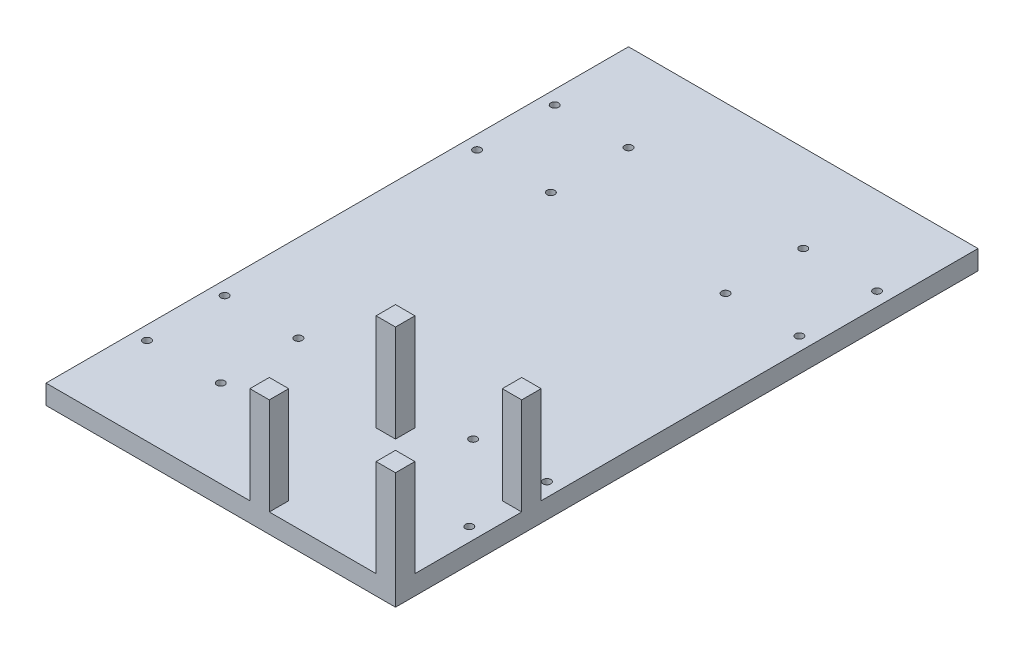
SolidWorks part; units mm, degrees
material "Pine"
ref_plane "Front Plane" through (0, 0, 0) normal (0, 0, 1) x (1, 0, 0)
ref_plane "Top Plane" through (0, 0, 0) normal (0, 1, 0) x (1, 0, 0)
ref_plane "Right Plane" through (0, 0, 0) normal (1, 0, 0) x (0, 0, -1)
sketch "Sketch3" plane through (0, 0, 0) normal (0, 1, 0) x (1, 0, 0)
  line L1 (-90, -150) -> (90, -150)
  line L2 (-90, -150) -> (-90, 150)
  line L3 (-90, 150) -> (90, 150)
  line L4 (90, -150) -> (90, 150)
  line L5 (-90, -150) -> (90, 150) construction
  line L6 (-90, 150) -> (90, -150) construction
  point P0 (0, 0)
  dimension "D1" = 180
  dimension "D2" = 300
extrude "Boss-Extrude1" add sketch "Sketch3" along normal blind 10
sketch "Sketch4" plane through (0, 10, 0) normal (0, 1, 0) x (1, 0, 0)
  line L0 (90, -150) -> (90, 150) construction
  line L1 (90, -150) -> (80, -150)
  line L2 (90, -150) -> (90, -140)
  line L3 (90, -75) -> (80, -75)
  line L4 (15, -150) -> (15, -140)
  line L5 (-90, -150) -> (90, -150) construction
  line L6 (25, -150) -> (25, -140)
  line L7 (80, -75) -> (80, -85)
  line L8 (25, -75) -> (15, -75)
  line L9 (25, -150) -> (15, -150)
  line L10 (15, -140) -> (25, -140)
  line L11 (15, -85) -> (25, -85)
  line L12 (80, -85) -> (90, -85)
  line L13 (80, -140) -> (90, -140)
  line L14 (15, -85) -> (15, -75)
  line L15 (25, -85) -> (25, -75)
  line L16 (80, -140) -> (80, -150)
  line L17 (90, -85) -> (90, -75)
  point P20 (85, -140)
  dimension "D1" = 0
  dimension "D2" = 0
  dimension "D3" = 75
  dimension "D4" = 75
  dimension "D5" = 10
  dimension "D6" = 10
  dimension "D7" = 10
  dimension "D8" = 10
  dimension "D9" = 10
extrude "Boss-Extrude2" add sketch "Sketch4" along normal blind 50
sketch "Sketch7" plane through (0, 0, 0) normal (0, -1, 0) x (1, 0, 0)
  line L0 (90, 150) -> (90, -150) construction
  line L1 (-90, 150) -> (90, 150) construction
  circle A0 centre (45, -105) radius 2
  circle A1 centre (83, -105) radius 2
  circle A2 centre (83, -65) radius 2
  circle A3 centre (45, -65) radius 2
  circle A4 centre (-45, -65) radius 2
  circle A5 centre (-83, -65) radius 2
  circle A6 centre (-45, -105) radius 2
  circle A7 centre (-83, -105) radius 2
  circle A8 centre (-83, 65) radius 2
  circle A9 centre (-83, 105) radius 2
  circle A10 centre (-45, 105) radius 2
  circle A11 centre (-45, 65) radius 2
  circle A12 centre (45, 105) radius 2
  circle A13 centre (83, 105) radius 2
  circle A14 centre (83, 65) radius 2
  circle A15 centre (45, 65) radius 2
  dimension "D17" = 40
  dimension "D1" = 38
  dimension "D2" = 40
  dimension "D3" = 38
  dimension "D4" = 90
  dimension "D5" = 38
  dimension "D6" = 40
  dimension "D7" = 38
  dimension "D8" = 130
  dimension "D9" = 38
  dimension "D10" = 40
  dimension "D11" = 38
  dimension "D12" = 90
  dimension "D13" = 38
  dimension "D14" = 40
  dimension "D15" = 38
  dimension "D16" = 7
  dimension "D18" = 55.1725
  dimension "D19" = 40
  dimension "D20" = 55.1725
  dimension "D21" = 40
  dimension "D22" = 40
  dimension "D23" = 55.1725
  dimension "D24" = 55.1725
  dimension "D25" = 90
  dimension "D26" = 90
  dimension "D27" = 45
extrude "Cut-Extrude2" cut sketch "Sketch7" against normal blind 10
sketch "Sketch8" plane through (0, 10, 0) normal (0, 1, 0) x (1, 0, 0)
  line L0 (-90, -150) -> (15, -150) construction
  line L1 (-90, 150) -> (-90, -150) construction
  line L2 (90, -75) -> (90, 150) construction
  circle A0 centre (-25, -45) radius 4
  circle A1 centre (-5, -45) radius 4
  circle A5 centre (-25, 30) radius 4
  circle A6 centre (-5, 30) radius 4
  circle A7 centre (35, -7.5) radius 4
  circle A8 centre (55, -7.5) radius 4
  point P4 (-22.8322, 0)
  point P5 (-22.3959, -42.1938)
  point P6 (0, 0)
  point P9 (-29.0111, 0)
  point P12 (-2.3959, 28.1702)
  point P17 (57.4077, -4.1346)
  dimension "D1" = 8
  dimension "D2" = 8
  dimension "D4" = 8
  dimension "D5" = 8
  dimension "D7" = 8
  dimension "D8" = 8
  dimension "D3" = 20
  dimension "D6" = 20
  dimension "D9" = 20
  dimension "D10" = 105
  dimension "D11" = 65
  dimension "D12" = 65
  dimension "D13" = 75
  dimension "D14" = 37.5
  dimension "D15" = 35
extrude "Cut-Extrude3" [suppressed] cut sketch "Sketch8" against normal blind 10
